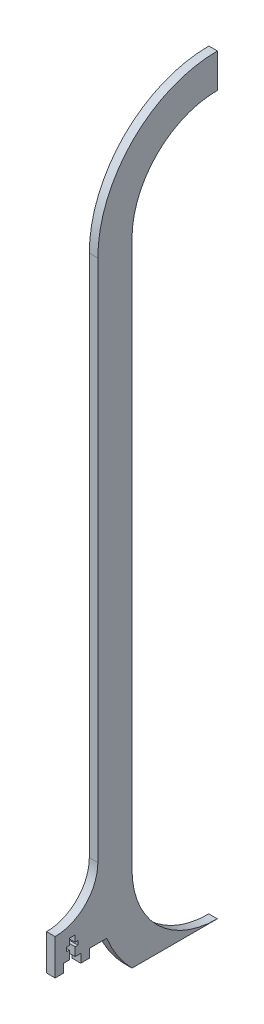
SolidWorks part; units mm, degrees
ref_plane "Front Plane" through (0, 0, 0) normal (0, 0, 1) x (1, 0, 0)
ref_plane "Top Plane" through (0, 0, 0) normal (0, 1, 0) x (1, 0, 0)
ref_plane "Right Plane" through (0, 0, 0) normal (1, 0, 0) x (0, 0, -1)
sketch "Elevator Ball Support Rail" plane through (0, 0, 0) normal (1, 0, 0) x (0, 0, -1)
  line L0 (63.5, 266.7) -> (63.5, 292.1)
  line L1 (63.5, 463.0976) -> (63.5, -266.7) construction
  line L2 (63.5, -266.7) -> (0, -266.7)
  line L3 (-31.75, -238.125) -> (-18.7887, -238.125)
  line L4 (-38.1, -244.475) -> (-31.75, -244.475)
  line L5 (-38.1, -238.125) -> (-38.1, -244.475)
  line L6 (0, 203.2) -> (0, -203.2)
  line L7 (-25.4, -186.055) -> (-25.4, -296.4291) construction
  line L8 (0, -203.2) -> (0, -313.4298) construction
  line L9 (-31.75, -238.125) -> (-31.75, -244.475)
  line L10 (-50.8, -238.125) -> (-46.609, -238.125)
  line L11 (-25.4, 203.2) -> (-25.4, -186.055)
  line L12 (-57.15, -217.805) -> (-57.15, -244.475)
  line L13 (-57.15, -244.475) -> (-50.8, -244.475)
  line L14 (-42.291, -238.125) -> (-38.1, -238.125)
  line L15 (-50.8, -244.475) -> (-50.8, -238.125)
  line L16 (-42.291, -231.775) -> (-42.291, -238.125)
  line L17 (-42.291, -231.775) -> (-40.25, -231.775)
  line L18 (-40.25, -231.775) -> (-40.25, -228.875)
  line L19 (-42.291, -228.875) -> (-42.291, -224.155)
  line L20 (-42.291, -224.155) -> (-46.609, -224.155)
  line L21 (-40.25, -228.875) -> (-42.291, -228.875)
  line L22 (-48.65, -228.875) -> (-48.65, -231.775)
  line L23 (-48.65, -231.775) -> (-46.609, -231.775)
  line L24 (-46.609, -231.775) -> (-46.609, -238.125)
  line L25 (-46.609, -224.155) -> (-46.609, -228.875)
  line L26 (-46.609, -228.875) -> (-48.65, -228.875)
  arc A0 (0, 203.2) -> (63.5, 266.7) centre (63.5, 203.2) cw
  arc A1 (63.5, 292.1) -> (-25.4, 203.2) centre (63.5, 203.2) ccw
  arc A2 (0, -203.2) -> (63.5, -266.7) centre (63.5, -203.2) ccw
  arc A3 (-18.7887, -238.125) -> (0, -266.7) centre (63.5, -204.483) ccw
  arc A4 (-57.15, -217.805) -> (-25.4, -186.055) centre (-57.15, -186.055) ccw
  point P4 (0, 0)
  dimension "D5" = 25.4
  dimension "D4" = 63.5
  dimension "D7" = 63.5
  dimension "D8" = 6.35
  dimension "D14" = 12.7
  dimension "D13" = 6.35
  dimension "D6" = 6.35
  dimension "D1" = 25.4
  dimension "D2" = 63.5
  dimension "D3" = 406.4
  dimension "D9" = 22.225
  dimension "D10" = 6.35
  dimension "D11" = 6.35
  dimension "D12" = 6.35
  dimension "D15" = 2.9
  dimension "D16" = 8.4
  dimension "D17" = 6.35
  dimension "D18" = 4.318
  dimension "D19" = 13.97
extrude "Boss-Extrude2" add sketch "Elevator Ball Support Rail" along normal blind 6.35 contours L5 L4 L9 L3 A3 L2 A2 L6 A0 L0 A1 L11 A4 L12 L13 L15 L10 L24 L23 L22 L26 L25 L20 L19 L21 L18 L17 L16 L14
equation "\"Ball Diameter\"= 1.75in"
equation "\"Pulley Diameter\" = 1in"
equation "\"Reactor Height\" = 14in"
equation "\"Sheet Thickness\"= 0.25in"
equation "\"Screw Diameter\"= .17in"
equation "\"Robot Diameter\"= 16in"
equation "\"Castor Screw Diameter\"= 0.22in"
equation "\"Wheel Diameter\" = 4in"
equation "\"Nut Diameter\" = 8.4mm"
equation "\"Nut Height\" = 2.9mm"
equation "\"Screw Height\" = 0.55in"
equation "\"D11@Elevator Ball Support Rail\"=\"Sheet Thickness\""
equation "\"Elevator Height\" = 11.5in"
equation "\"D12@Elevator Ball Support Rail\"=\"Sheet Thickness\""
equation "\"D7@Elevator Ball Support Rail\"=(\"Pulley Diameter\"/2) + \"Ball Diameter\" + 0.25in"
equation "\"D10@Elevator Ball Support Rail\"=\"Sheet Thickness\""
equation "\"D13@Elevator Ball Support Rail\"=\"Sheet Thickness\""
equation "\"D1@T-Slot\" = \"Screw Diameter\""
equation "\"D16@Elevator Ball Support Rail\"=\"Nut Diameter\""
equation "\"D15@Elevator Ball Support Rail\"=\"Nut Height\""
equation "\"D16@Elevator Ball Support Rail\" = \"Nut Diameter\""
equation "\"D9@Elevator Ball Support Rail\"=\"Ball Diameter\"/2"
equation "\"D1@Boss-Extrude2\"=\"Sheet Thickness\""
equation "\"D18@Elevator Ball Support Rail\"=\"Screw Diameter\""
equation "\"D19@Elevator Ball Support Rail\"=\"Screw Height\""
